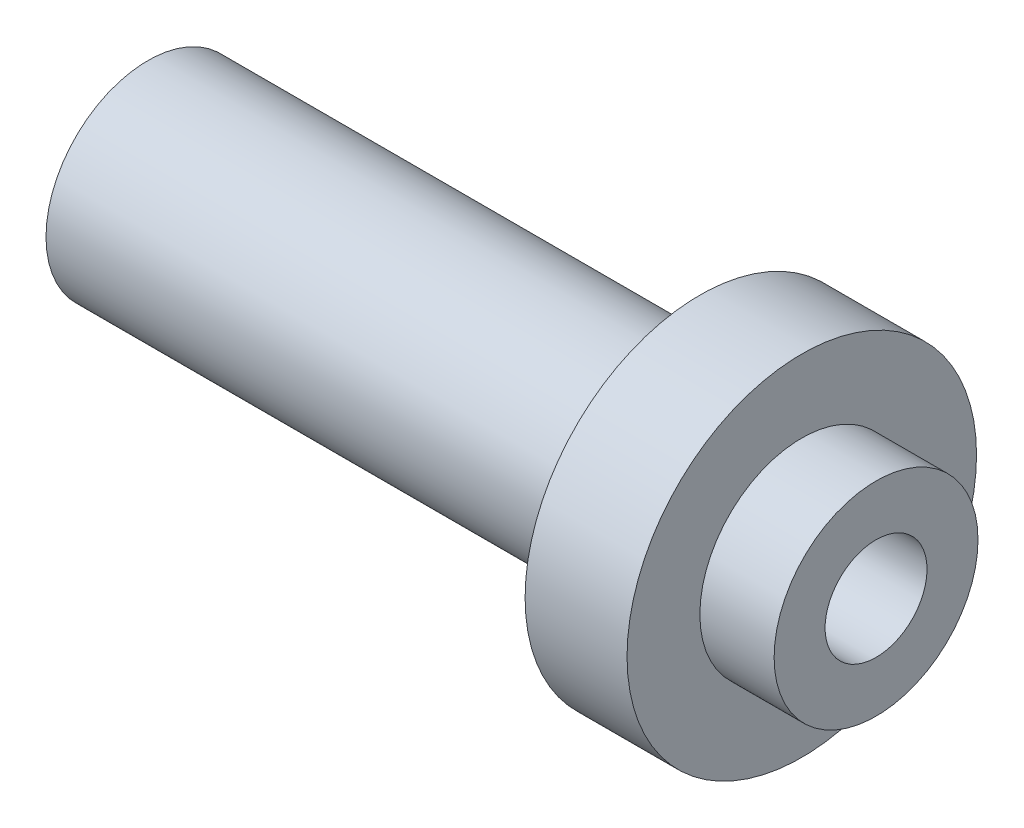
SolidWorks part; units mm, degrees
ref_plane "Front Plane" through (0, 0, 0) normal (0, 0, 1) x (1, 0, 0)
ref_plane "Top Plane" through (0, 0, 0) normal (0, 1, 0) x (1, 0, 0)
ref_plane "Right Plane" through (0, 0, 0) normal (1, 0, 0) x (0, 0, -1)
sketch "Sketch1" plane through (0, 0, 0) normal (0, 0, 1) x (1, 0, 0)
  line L0 (-5.1, 12) -> (-5.1, 7)
  line L1 (-5.1, 12) -> (-12.1, 12)
  line L2 (-12.1, 12) -> (-12.1, 7)
  line L3 (-12.1, 7) -> (-50, 7)
  line L4 (-50, 7) -> (-50, 0)
  line L5 (-78.3439, 0) -> (16.242, 0) construction
  line L6 (-5.1, 7) -> (0, 7)
  line L7 (0, 7) -> (0, 0)
  line L8 (-50, 0) -> (0, 0)
  dimension "D1" = 7
  dimension "D2" = 7
  dimension "D3" = 5
  dimension "D4" = 5.1
  dimension "D5" = 7
  dimension "D6" = 50
  dimension "D8" = 7
revolve "Revolve1" add sketch "Sketch1" angle 360 about L5
sketch "Sketch2" plane through (0, 0, 0) normal (1, 0, 0) x (0, 0, -1)
  circle A0 centre (0, 0) radius 3.5
  dimension "D1" = 7
ref_axis "Axis1" through (-412.2425, 0, 0) along (1, 0, 0)
ref_plane "Plane1" through (0, 12, 0) normal (0, 1, 0) x (1, 0, 0)
ref_plane "Plane2" through (0, 0, 12) normal (0, 0, 1) x (1, 0, 0)
hole_wizard "Trou taraudé M8x1.01" positions "Esquisse1" profile "Esquisse3" tap size "M8x1.0" standard "ISO"
sketch "Esquisse1" plane through (0, 0, 0) normal (1, 0, 0) x (0, 0, -1)
  point P0 (0, 0)
sketch "Esquisse3" plane through (0, 0, 0) normal (0, 1, 0) x (0, 0, -1)
  line L0 (0, 0) -> (0, 32.103)
  line L1 (0, 32.103) -> (3.5, 30)
  line L2 (3.5, 30) -> (3.5, 0)
  line L5 (3.5, 0) -> (0, 0)
  line L10 (0, 32.103) -> (-3.5, 30) construction
  line L11 (0, -6.35) -> (0, 107.95) construction
  dimension "Diamètre du trou pour taraudage" = 7
  dimension "Profondeur du trou pour taraudage" = 30
  dimension "Angle de pointe" = 118
cosmetic thread "Filetage de perçage1" parameters "D1"=25, "D2"=8
